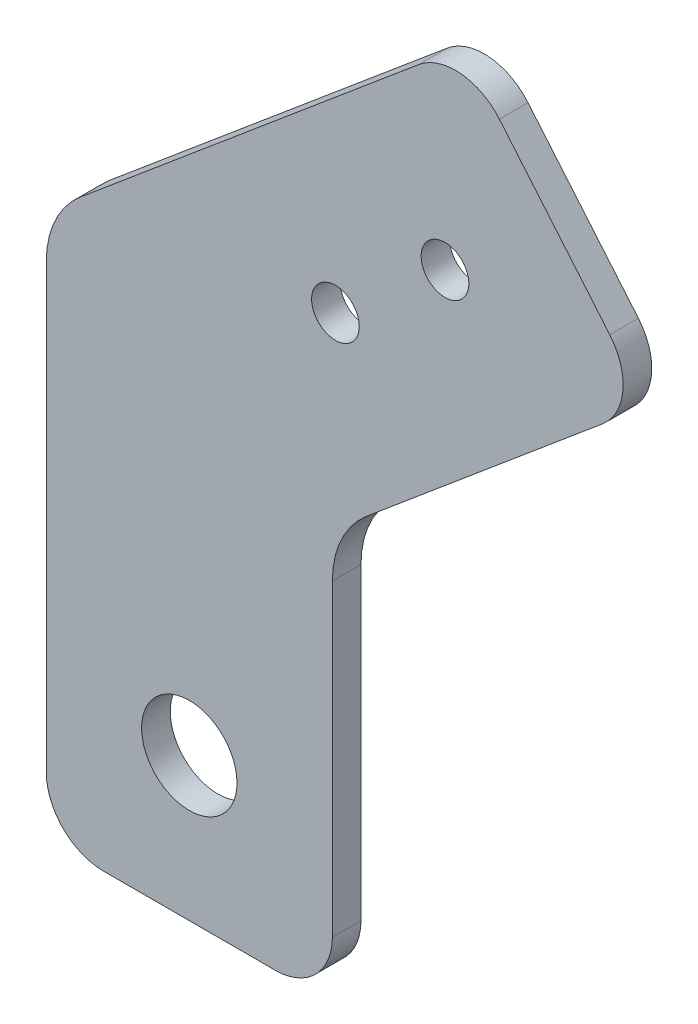
SolidWorks part; units mm, degrees
material "Plain Carbon Steel"
ref_plane "Front Plane" through (0, 0, 0) normal (0, 0, 1) x (1, 0, 0)
ref_plane "Top Plane" through (0, 0, 0) normal (0, 1, 0) x (1, 0, 0)
ref_plane "Right Plane" through (0, 0, 0) normal (1, 0, 0) x (0, 0, -1)
sketch "Sketch1" plane through (0, 0, 0) normal (0, 0, 1) x (1, 0, 0)
  line L0 (0, 0) -> (0, -28.3801) construction
  line L1 (0, 0) -> (-38.3022, -32.1394) construction
  line L2 (-38.3022, -32.1394) -> (-38.3022, -67.1394) construction
  line L3 (-14.2381, 7.6339) -> (-49.7301, -22.1474)
  line L4 (-53.3022, -29.8078) -> (-53.3022, -48.5616)
  line L5 (5.0455, -15.3474) -> (-19.7301, -36.1366)
  line L6 (-23.3022, -43.7971) -> (-23.3022, -48.5616)
  line L7 (5.7851, -6.8944) -> (-5.7851, 6.8944)
  line L8 (-53.3022, -25.1448) -> (-53.3022, -67.1394) construction
  line L9 (-23.3022, -39.134) -> (-23.3022, -67.1394) construction
  line L10 (-9.6418, 11.4907) -> (-53.3022, -25.1448) construction
  line L11 (9.6418, -11.4907) -> (-23.3022, -39.134) construction
  line L13 (-23.3022, -48.5616) -> (-23.3022, -76.1394)
  line L14 (-29.3022, -82.1394) -> (-47.3022, -82.1394)
  line L15 (-53.3022, -76.1394) -> (-53.3022, -48.5616)
  circle A1 centre (-38.3022, -67.1394) radius 5
  arc A4 (-49.7301, -22.1474) -> (-53.3022, -29.8078) centre (-43.3022, -29.8078) ccw
  arc A5 (-19.7301, -36.1366) -> (-23.3022, -43.7971) centre (-13.3022, -43.7971) ccw
  circle A6 centre (-11.4907, -9.6418) radius 2.5
  circle A7 centre (-22.9813, -19.2836) radius 2.5
  arc A11 (-47.3022, -82.1394) -> (-53.3022, -76.1394) centre (-47.3022, -76.1394) cw
  arc A12 (-23.3022, -76.1394) -> (-29.3022, -82.1394) centre (-29.3022, -76.1394) cw
  arc A13 (5.0455, -15.3474) -> (5.7851, -6.8944) centre (1.1888, -10.7511) ccw
  arc A14 (-14.2381, 7.6339) -> (-5.7851, 6.8944) centre (-10.3814, 3.0377) cw
  dimension "D7" = 2
  dimension "D6" = 6
  dimension "D4" = 15
  dimension "D8" = 10
  dimension "D1" = 50
  dimension "D5" = 130
  dimension "D9" = 30
  dimension "D10" = 15
  dimension "D11" = 50
  dimension "32" = 35
  dimension "D2" = 15
  dimension "D3" = 15
base flange "Base-Flange1" sketch "Sketch1" thickness 3 reverse thickness direction no parameters "D1"=0.7366
sketch "Sketch10" [suppressed] plane through (0, 0, -3) normal (0, 0, -1) x (-1, 0, 0)
  line L0 (28.4978, -44.7167) -> (58.4978, -30.7274)
  line L2 (55.8626, -27.2932) -> (9.6418, 11.4907)
  line L3 (9.6418, 11.4907) -> (-9.6418, -11.4907)
  line L4 (-9.6418, -11.4907) -> (25.8626, -41.2824)
  arc A0 (29.4347, -48.9428) -> (25.8626, -41.2824) centre (19.4347, -48.9428) ccw construction
  arc A1 (59.4347, -34.9536) -> (55.8626, -27.2932) centre (49.4347, -34.9536) ccw construction
  arc A2 (25.8626, -41.2824) -> (28.4978, -44.7167) centre (19.4347, -48.9428) cw
  arc A3 (55.8626, -27.2932) -> (58.4978, -30.7274) centre (49.4347, -34.9536) cw
  circle A4 centre (11.4907, -9.6418) radius 2.5
  circle A5 centre (22.9813, -19.2836) radius 2.5
  circle A6 centre (34.472, -28.9254) radius 2.5
sketch "Bend-Lines1" [suppressed] plane through (0, 0, 0) normal (0, 1, 0) x (1, 0, 0)
sketch "Bounding-Box1" [suppressed] plane through (0, 0, 0) normal (0, 1, 0) x (1, 0, 0)
sheet metal parameters "Sheet-Metal1" thickness 3 parameters "D1"=0.7366
flat pattern "Flat-Pattern1" [suppressed]
sketch "Bend-Lines2" plane through (0, 0, 0) normal (0, 0, 1) x (1, 0, 0)
sketch3d "Bounding-Box2" [suppressed]
  line L0 (22.7265, -84.0969, 0) -> (79.7922, 36.95, 0) construction
  line L1 (-37.3497, -55.7749, 0) -> (19.716, 65.272, 0) construction
  line L2 (22.7265, -84.0969, 0) -> (-37.3497, -55.7749, 0) construction
  line L3 (79.7922, 36.95, 0) -> (19.716, 65.272, 0) construction
sketch "Sketch10-2" [suppressed] plane through (0, 0, -3) normal (0, 0, -1) x (-1, 0, 0)
  line L0 (28.4978, -44.7167) -> (58.4978, -30.7274)
  line L2 (55.8626, -27.2932) -> (9.6418, 11.4907)
  line L3 (9.6418, 11.4907) -> (-9.6418, -11.4907)
  line L4 (-9.6418, -11.4907) -> (25.8626, -41.2824)
  arc A2 (25.8626, -41.2824) -> (28.4978, -44.7167) centre (19.4347, -48.9428) cw
  arc A3 (55.8626, -27.2932) -> (58.4978, -30.7274) centre (49.4347, -34.9536) cw
  circle A4 centre (11.4907, -9.6418) radius 2.5
  circle A5 centre (22.9813, -19.2836) radius 2.5
  circle A6 centre (34.472, -28.9254) radius 2.5
